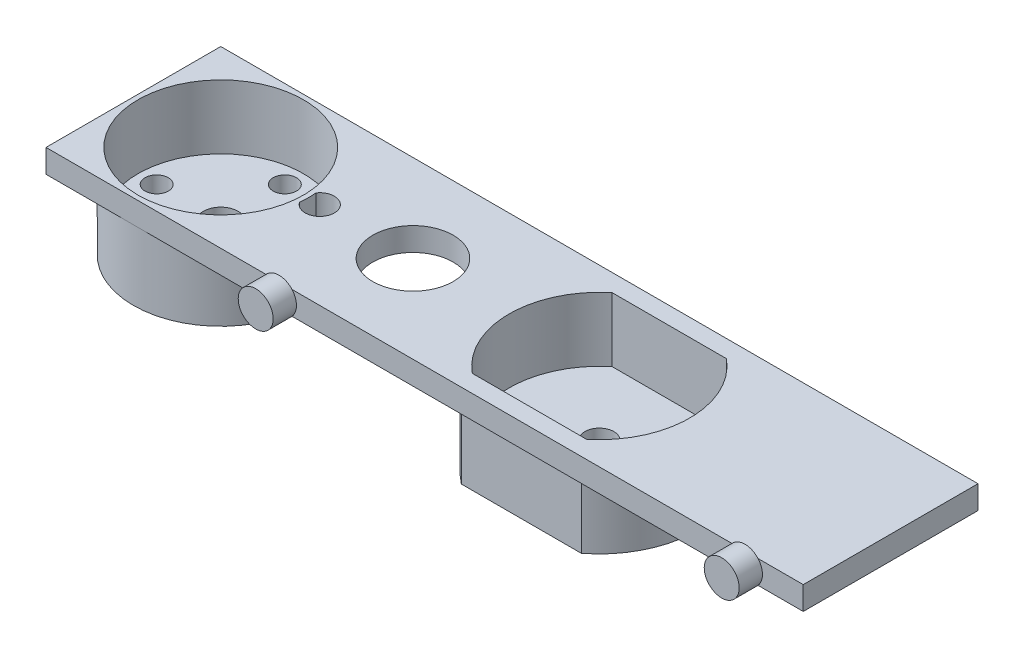
SolidWorks part; units mm, degrees
ref_plane "前视基准面" through (0, 0, 0) normal (0, 0, 1) x (1, 0, 0)
ref_plane "上视基准面" through (0, 0, 0) normal (0, 1, 0) x (1, 0, 0)
ref_plane "右视基准面" through (0, 0, 0) normal (1, 0, 0) x (0, 0, -1)
other "Configuration Table"
sketch "草图1" plane through (0, 0, 0) normal (0, 1, 0) x (1, 0, 0)
  line L0 (0, 7.5) -> (0, -7.5) construction
  line L1 (-25, 7.5) -> (25, 7.5)
  line L2 (-25, 7.5) -> (-25, -7.5)
  line L3 (-25, -7.5) -> (25, -7.5)
  line L4 (25, 7.5) -> (25, -7.5)
  line L5 (-25, 0) -> (25, 0) construction
  line L7 (-25, -7.5) -> (-40, -7.5)
  line L10 (-25, -7.5) -> (-25, 7.5)
  line L11 (-25, 7.5) -> (-40, 7.5)
  line L12 (-40, -7.5) -> (-40, 7.5)
  line L14 (-25, 7.5) -> (-40, 7.5)
  dimension "D1" = 50
  dimension "D2" = 15
  dimension "D6" = 15
  dimension "D7" = 15
extrude "凸台-拉伸1" add sketch "草图1" along normal blind 2 contours L11 L2 | L2 L1 L4 L3 | L10 L7 L12 L11 region at (-32.5, 0, 0)
sketch "草图2" plane through (0, 0, 0) normal (0, 1, 0) x (1, 0, 0)
  line L0 (0, 7.5) -> (0, -7.5) construction
  line L1 (25, 7.5) -> (-40, 7.5) construction
  line L2 (-32.5, 7.5) -> (-32.5, -7.5) construction
  line L3 (-40, -7.5) -> (-40, 7.5) construction
  line L4 (-25, 7.5) -> (-25, -7.5) construction
  line L6 (-25, -7.5) -> (25, -7.5) construction
  line L10 (-40, 0) -> (-25, 0) construction
  line L14 (-40, -7.5) -> (25, -7.5) construction
  circle A2 centre (0, 0) radius 1.25
  circle A3 centre (16, 0) radius 4.1
  circle A4 centre (16, 0) radius 3.45
  circle A5 centre (-16, 0) radius 4.1
  circle A6 centre (-16, 0) radius 3.45
  circle A8 centre (24, 0) radius 1.25
  circle A9 centre (-24, 0) radius 1.25
  circle A11 centre (-32.5, 0) radius 1.5
  circle A12 centre (-27, 0) radius 1
  circle A13 centre (-32.5, -5.5) radius 1
  circle A14 centre (-38, 0) radius 1
  circle A15 centre (-32.5, 5.5) radius 1
  point P36 (0, -7.5)
  dimension "D3" = 2.5
  dimension "D4" = 6.9
  dimension "D5" = 8.2
  dimension "D7" = 15
  dimension "D8" = 2.5
  dimension "D11" = 3
  dimension "D12" = 2
  dimension "D2" = 7.5
  dimension "D6" = 16
  dimension "D10" = 8
  dimension "D13" = 5.5
  dimension "D17" = 7.5
  dimension "D14" = 4
extrude "切除-拉伸1" cut sketch "草图2" along normal up to surface (2 mm away) contours A2 | A9 | A6 | A14 | A11 | A13 | A12 | A15 up to face at (-7.5, 2, 0)
sketch "草图4" plane through (0, 0, 7.5) normal (0, 0, 1) x (1, 0, 0)
  line L0 (25, 1) -> (-40, 1) construction
  line L1 (25, 2) -> (25, 0) construction
  line L2 (-40, 2) -> (-40, 0) construction
  line L3 (0, 0) -> (0, 2) construction
  line L5 (25, 2) -> (25, 0) construction
  line L6 (-40, 2) -> (25, 2) construction
  circle A0 centre (20, 1) radius 1.5
  circle A1 centre (-20, 1) radius 1.5
  dimension "D1" = 3
  dimension "D2" = 3
  dimension "D3" = 20
  dimension "D4" = 20
  dimension "D5" = 25
extrude "凸台-拉伸2" add sketch "草图4" along normal blind 2
sketch "草图5" plane through (0, 2, 0) normal (0, 1, 0) x (1, 0, 0)
  line L0 (0, 0) -> (0, 4.126) construction
  line L1 (4.9054, -6) -> (-4.9054, -6)
  line L2 (-4.7026, 0) -> (-2.9861, 0) construction
  line L3 (4.9054, 6) -> (-4.9054, 6)
  line L4 (5.149, -6.7) -> (-5.149, -6.7)
  line L5 (5.149, 6.7) -> (-5.149, 6.7)
  arc A0 (-4.9054, 6) -> (-4.9054, -6) centre (0, 0) ccw
  arc A1 (4.9054, -6) -> (4.9054, 6) centre (0, 0) ccw
  arc A2 (-5.149, 6.7) -> (-5.149, -6.7) centre (0, 0) ccw
  arc A3 (5.149, -6.7) -> (5.149, 6.7) centre (0, 0) ccw
  circle A4 centre (-32.5, 0) radius 7.1
  circle A5 centre (-32.5, 0) radius 7.5
  point P14 (0, -6)
  point P15 (0, 6)
  point P21 (0, -6.7)
  point P22 (0, 6.7)
  circle M2 centre (-32.5, 5.5) radius 1
  circle M3 centre (-38, 0) radius 1
  circle M4 centre (-32.5, 0) radius 1.5
  circle M5 centre (-32.5, -5.5) radius 1
  circle M6 centre (-27, 0) radius 1
  circle M9 centre (0, 0) radius 1.25
  dimension "D1" = 15.5
  dimension "D3" = 16.9
  dimension "D5" = 14.2
  dimension "D6" = 15
  dimension "D2" = 12
  dimension "D4" = 13.4
extrude "凸台-拉伸3" add sketch "草图5" against normal blind 8
extrude "凸台-拉伸4" add sketch "草图5<5>" against normal up to surface (8 mm away) contours L1 A1 L3 A0 M9 | A4 M2 M3 M4 M6 M5 region at (0, 2, 5.804) region at (-39.3992, 2, 0) up to face at (0, -6, 0)
sketch "草图5<5>" plane through (0, 2, 0) normal (0, 1, 0) x (1, 0, 0) same geometry as "草图5"
extrude "切除-拉伸3" cut sketch "草图5<6>" against normal offset from surface (5.5 mm away) 2.5 contours L1 A1 L3 A0 M9 | A4 region at (0, 2, 5.804) up to face at (0, -6, 0)
sketch "草图5<6>" plane through (0, 2, 0) normal (0, 1, 0) x (1, 0, 0) same geometry as "草图5"
